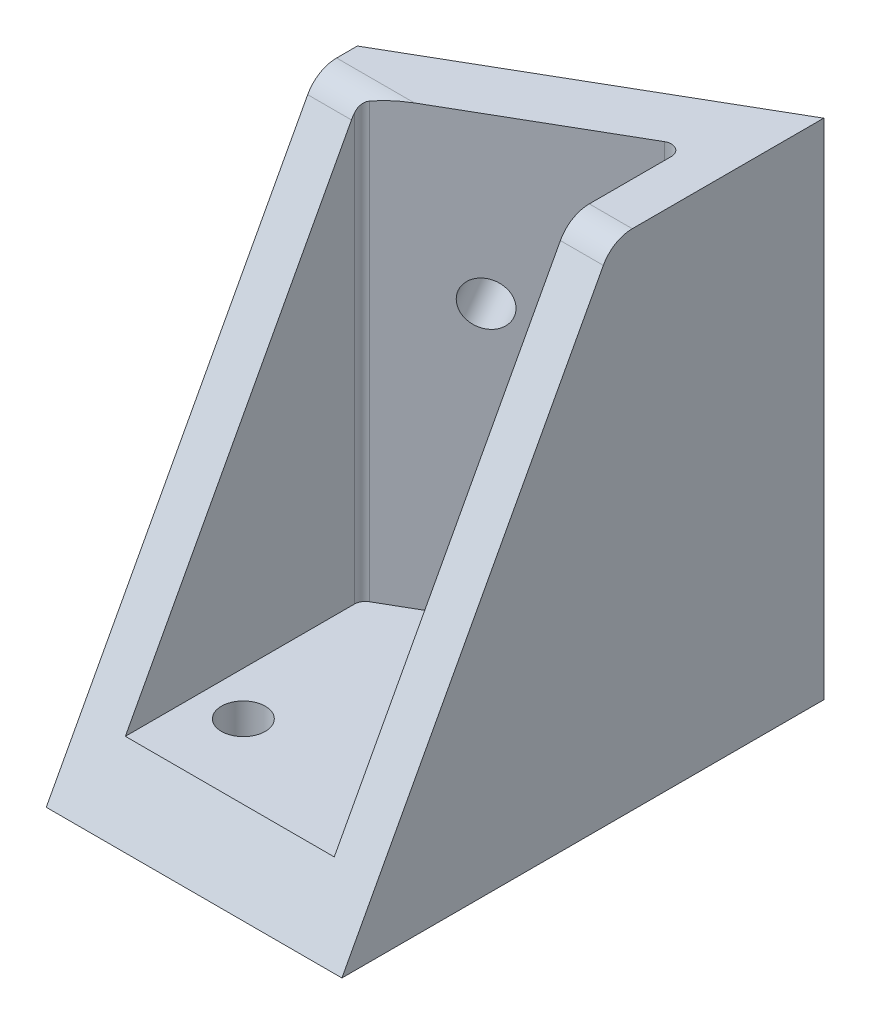
SolidWorks part; units mm, degrees
ref_plane "Front Plane" through (0, 0, 0) normal (0, 0, 1) x (1, 0, 0)
ref_plane "Top Plane" through (0, 0, 0) normal (0, 1, 0) x (1, 0, 0)
ref_plane "Right Plane" through (0, 0, 0) normal (1, 0, 0) x (0, 0, -1)
sketch "Sketch1" plane through (0, 0, 0) normal (0, 1, 0) x (1, 0, 0)
  line L1 (-13.5, -22) -> (13.5, -22)
  line L2 (-13.5, -22) -> (-13.5, 22)
  line L3 (-13.5, 22) -> (13.5, 22)
  line L4 (13.5, -22) -> (13.5, 22)
  line L5 (-13.5, -22) -> (13.5, 22) construction
  line L6 (-13.5, 22) -> (13.5, -22) construction
  point P0 (0, 0)
  dimension "D1" = 27
  dimension "D2" = 44
extrude "Boss-Extrude1" add sketch "Sketch1" along normal blind 6
sketch "Sketch2" plane through (0, 6, 0) normal (0, 1, 0) x (1, 0, 0)
  line L0 (13.5, 22) -> (-13.5, 6.4115)
  line L1 (-13.5, 22) -> (-13.5, -22) construction
  line L2 (-13.5, 6.4115) -> (-13.5, 22)
  line L3 (-13.5, 22) -> (13.5, 22)
  dimension "D1" = 30
extrude "Cut-Extrude1" cut sketch "Sketch2" against normal through all
sketch "Sketch4" plane through (0, 6, 0) normal (0, 1, 0) x (1, 0, 0)
  line L0 (-13.5, 6.4115) -> (-13.5, 0.4115)
  line L1 (-13.5, 6.4115) -> (-13.5, -22) construction
  line L2 (-13.5, 0.4115) -> (13.5, 16)
  line L3 (13.5, -22) -> (13.5, 22) construction
  line L4 (13.5, 16) -> (13.5, 22)
  line L5 (13.5, 22) -> (-13.5, 6.4115)
  dimension "D1" = 6
  dimension "D2" = 6
extrude "Boss-Extrude2" add sketch "Sketch4" along normal blind 40
sketch "Sketch5" plane through (0, 6, 0) normal (0, 1, 0) x (1, 0, 0)
  line L1 (-13.5, 0.4115) -> (-13.5, -22) construction
  line L2 (-13.5, -22) -> (13.5, -22) construction
  circle A0 centre (-5.5, -12) radius 2
  circle A1 centre (4.5, -2) radius 2
  dimension "D4" = 4
  dimension "D5" = 4
  dimension "D3" = 8
  dimension "D1" = 10
  dimension "D2" = 10
  dimension "D6" = 10
sketch "Sketch6" plane through (-6.1513, 0, -10.6543) normal (-0.5, 0, -0.866) x (-0.866, 0, 0.5)
  line L0 (-22.6913, 46) -> (8.4856, 46) construction
  line L2 (8.4856, 0) -> (8.4856, 46) construction
  circle A0 centre (-6.5144, 18.5) radius 2
  circle A1 centre (-1.5144, 31) radius 2
  dimension "D5" = 4
  dimension "D6" = 4
  dimension "D1" = 12.5
  dimension "D2" = 15
  dimension "D3" = 5
  dimension "D4" = 10
ref_plane "Plane1" through (-13.5, 0, 0) normal (-1, 0, 0) x (0, 0, 1)
ref_plane "Plane2" through (-9.5, 0, 0) normal (-1, 0, 0) x (0, 0, 1)
ref_plane "Plane3" through (13.5, 0, 0) normal (1, 0, 0) x (0, 0, -1)
ref_plane "Plane4" through (9.5, 0, 0) normal (1, 0, 0) x (0, 0, -1)
sketch "Sketch18" plane through (0, 6, 0) normal (0, 1, 0) x (1, 0, 0)
  line L0 (-13.5, -22) -> (-9.5, -22)
  line L1 (-13.5, 15.6263) -> (-13.5, -15.6263) construction
  line L2 (-13.5, -22) -> (13.5, -22) construction
  line L3 (-9.5, -22) -> (-9.5, 2.7209)
  line L4 (-13.5, 0.4115) -> (13.5, 16) construction
  line L5 (-9.5, 2.7209) -> (-13.5, 0.4115)
  line L6 (-13.5, 0.4115) -> (-13.5, -22)
  dimension "D1" = 4
extrude "Boss-Extrude3" add sketch "Sketch18" along normal up to surface (40 mm away) up to face at (0, 46, -11.2058)
sketch "Sketch19" plane through (0, 6, 0) normal (0, 1, 0) x (1, 0, 0)
  line L0 (13.5, 16) -> (9.576, 13.7345)
  line L1 (9.576, 13.7345) -> (9.576, -22)
  line L2 (-9.5, -22) -> (13.5, -22) construction
  line L3 (9.576, -22) -> (13.5, -22)
  line L4 (13.5, -22) -> (13.5, 16)
  line L8 (-9.5, 2.7209) -> (13.5, 16) construction
extrude "Boss-Extrude5" add sketch "Sketch19" along normal up to surface (40 mm away) up to face at (-3.1667, 46, -0.5221)
extrude "Cut-Extrude2" cut sketch "Sketch6" against normal blind 10
sketch "Sketch20" plane through (-13.5, 0, 0) normal (-1, 0, 0) x (0, 0, 1)
  line L0 (22, 0) -> (-2.7215, 46)
  line L1 (-6.4115, 46) -> (22, 46) construction
  line L2 (-6.4115, 0) -> (-6.4115, 46) construction
  line L3 (-2.7215, 46) -> (22, 46)
  line L4 (22, 46) -> (22, 0)
  dimension "D1" = 3.69
extrude "Cut-Extrude3" cut sketch "Sketch20" against normal through all
fillet "Fillet1" radius 1 2 edges at (-9.5, 25.9994, -2.7209) (9.576, 26, -13.7345)
extrude "Cut-Extrude4" cut sketch "Sketch5" against normal through all
fillet "Fillet2" radius 3 2 edges at (11.538, 46, -2.7215) (-11.408, 46, -2.7215)
